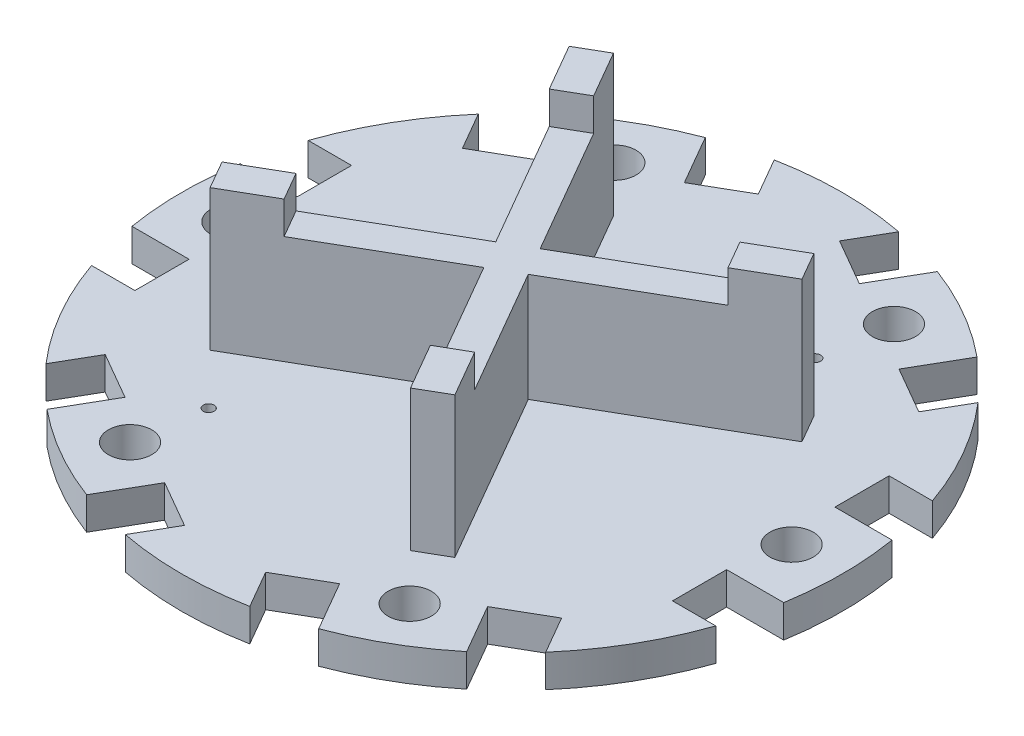
SolidWorks part; units mm, degrees
ref_plane "Alzado" through (0, 0, 0) normal (0, 0, 1) x (1, 0, 0)
ref_plane "Planta" through (0, 0, 0) normal (0, 1, 0) x (1, 0, 0)
ref_plane "Vista lateral" through (0, 0, 0) normal (1, 0, 0) x (0, 0, -1)
sketch "Croquis1" plane through (0, 0, 0) normal (0, 1, 0) x (1, 0, 0)
  circle A0 centre (0, 0) radius 30.5
extrude "Saliente-Extruir1" add sketch "Croquis1" along normal blind 3
sketch "Croquis5" plane through (0, 3, 0) normal (0, 1, 0) x (1, 0, 0)
  line L1 (28.8141, -5) -> (30.0874, -5)
  line L2 (28.8141, 5) -> (30.0874, 5)
  line L3 (-24.8141, 10) -> (-28.8141, 10)
  line L4 (24.8141, -5) -> (24.8141, -10)
  line L5 (-24.8141, -10) -> (-28.8141, -10)
  line L6 (24.8141, -5) -> (28.8141, -5)
  line L7 (24.8141, 5) -> (24.8141, 10)
  line L8 (-24.8141, 5) -> (-28.8141, 5)
  line L9 (-24.8141, 5) -> (-24.8141, 10)
  line L10 (-24.8141, -5) -> (-28.8141, -5)
  line L11 (-24.8141, -5) -> (-24.8141, -10)
  line L12 (24.8141, 5) -> (28.8141, 5)
  line L13 (24.8141, -10) -> (28.8141, -10)
  line L14 (24.8141, 10) -> (28.8141, 10)
  line L15 (-28.8141, 5) -> (-30.0874, 5)
  line L16 (-28.8141, -5) -> (-30.0874, -5)
  line L17 (18.7372, 22.4537) -> (19.3738, 23.5564)
  line L18 (-24.8141, 0) -> (-12.407, -21.4896)
  line L19 (-12.407, -21.4896) -> (12.407, -21.4896)
  line L20 (12.407, -21.4896) -> (24.8141, 0)
  line L21 (24.8141, 0) -> (12.407, 21.4896)
  line L22 (12.407, 21.4896) -> (-12.407, 21.4896)
  line L23 (-12.407, 21.4896) -> (-24.8141, 0)
  line L24 (-21.0673, -16.4896) -> (-23.0673, -19.9537)
  line L25 (-3.7468, -26.4896) -> (-5.7468, -29.9537)
  line L26 (-16.7372, -18.9896) -> (-18.7372, -22.4537)
  line L27 (-16.7372, -18.9896) -> (-21.0673, -16.4896)
  line L28 (-8.0769, -23.9896) -> (-10.0769, -27.4537)
  line L29 (-8.0769, -23.9896) -> (-3.7468, -26.4896)
  line L30 (-18.7372, -22.4537) -> (-19.3738, -23.5564)
  line L31 (-10.0769, -27.4537) -> (-10.7136, -28.5564)
  line L32 (10.0769, 27.4537) -> (10.7136, 28.5564)
  line L33 (16.7372, 18.9896) -> (21.0673, 16.4896)
  line L34 (16.7372, 18.9896) -> (18.7372, 22.4537)
  line L35 (8.0769, 23.9896) -> (3.7468, 26.4896)
  line L36 (8.0769, 23.9896) -> (10.0769, 27.4537)
  line L37 (21.0673, 16.4896) -> (23.0673, 19.9537)
  line L38 (3.7468, 26.4896) -> (5.7468, 29.9537)
  line L39 (-3.7468, 26.4896) -> (-5.7468, 29.9537)
  line L40 (-21.0673, 16.4896) -> (-23.0673, 19.9537)
  line L41 (-8.0769, 23.9896) -> (-10.0769, 27.4537)
  line L42 (-8.0769, 23.9896) -> (-3.7468, 26.4896)
  line L43 (-16.7372, 18.9896) -> (-18.7372, 22.4537)
  line L44 (-16.7372, 18.9896) -> (-21.0673, 16.4896)
  line L45 (-10.0769, 27.4537) -> (-10.7136, 28.5564)
  line L46 (-18.7372, 22.4537) -> (-19.3738, 23.5564)
  line L47 (10.0769, -27.4537) -> (10.7136, -28.5564)
  line L48 (18.7372, -22.4537) -> (19.3738, -23.5564)
  line L49 (8.0769, -23.9896) -> (3.7468, -26.4896)
  line L50 (8.0769, -23.9896) -> (10.0769, -27.4537)
  line L51 (16.7372, -18.9896) -> (21.0673, -16.4896)
  line L52 (16.7372, -18.9896) -> (18.7372, -22.4537)
  line L53 (3.7468, -26.4896) -> (5.7468, -29.9537)
  line L54 (21.0673, -16.4896) -> (23.0673, -19.9537)
  circle A0 centre (0, 0) radius 21.4896 construction
  circle A1 centre (0, 0) radius 30.5 construction
  arc A2 (-28.8141, 10) -> (-30.0874, 5) centre (0, 0) ccw
  arc A3 (-5.7468, 29.9537) -> (-10.7136, 28.5564) centre (0, 0) ccw
  arc A4 (-30.0874, -5) -> (-28.8141, -10) centre (0, 0) ccw
  arc A5 (30.0874, -5) -> (28.8141, -10) centre (0, 0) cw
  arc A6 (28.8141, 10) -> (30.0874, 5) centre (0, 0) cw
  arc A7 (-23.0673, -19.9537) -> (-19.3738, -23.5564) centre (0, 0) ccw
  arc A8 (-10.7136, -28.5564) -> (-5.7468, -29.9537) centre (0, 0) ccw
  arc A9 (-19.3738, 23.5564) -> (-23.0673, 19.9537) centre (0, 0) ccw
  arc A10 (19.3738, 23.5564) -> (23.0673, 19.9537) centre (0, 0) cw
  arc A11 (5.7468, 29.9537) -> (10.7136, 28.5564) centre (0, 0) cw
  arc A12 (10.7136, -28.5564) -> (5.7468, -29.9537) centre (0, 0) cw
  arc A13 (23.0673, -19.9537) -> (19.3738, -23.5564) centre (0, 0) cw
  circle M2 centre (0, 0) radius 30.5
extrude "Cortar-Extruir3" cut sketch "Croquis5" against normal blind 4 contours L15 L8 L9 L3 M2 | L14 L7 L12 L2 M2 | L4 L13 L1 L6 M2 | L54 L51 L52 L48 M2 | L49 L53 L47 L50 M2 | L28 L31 L25 L29 M2 | L30 L26 L27 L24 M2 | L10 L16 L5 L11 M2 | L43 L46 L40 L44 M2 | L45 L41 L42 L39 M2 | L38 L35 L36 L32 M2 | L33 L37 L17 L34 M2 region at (27.1844, 3, 7.3876) region at (19.99, 3, 19.8486) region at (27.1844, 3, -7.3876) region at (7.1944, 3, 27.2362) region at (19.99, 3, -19.8486) region at (-7.1944, 3, 27.2362) region at (7.1944, 3, -27.2362) region at (-19.99, 3, 19.8486) region at (-7.1944, 3, -27.2362) region at (-27.1844, 3, 7.3876) region at (-19.99, 3, -19.8486) region at (-27.1844, 3, -7.3876)
sketch "Croquis7" plane through (0, 3, 0) normal (0, 1, 0) x (1, 0, 0)
  line L2 (25.8141, 0) -> (12.907, 22.3556)
  line L3 (12.907, 22.3556) -> (-12.907, 22.3556)
  line L4 (-12.907, 22.3556) -> (-25.8141, 0)
  line L5 (-25.8141, 0) -> (-12.907, -22.3556)
  line L6 (-12.907, -22.3556) -> (12.907, -22.3556)
  line L7 (12.907, -22.3556) -> (25.8141, 0)
  circle A0 centre (25.8141, 0) radius 2
  circle A4 centre (-25.8141, 0) radius 2
  circle A5 centre (0, 0) radius 22.3556 construction
  circle A6 centre (12.907, 22.3556) radius 2
  circle A7 centre (-12.907, -22.3556) radius 2
  circle A8 centre (-12.907, 22.3556) radius 2
  circle A9 centre (12.907, -22.3556) radius 2
extrude "Cortar-Extruir4" cut sketch "Croquis7" against normal blind 10 contours A8 L4 L3 | A4 L4 L5 | A4 L5 L4 | A8 L3 L4 | L2 A6 L3 | L3 A6 L2 | L7 A0 L2 | L2 A0 L7 | A7 L5 L6 | A7 L6 L5 | L6 A9 L7 | L7 A9 L6 | A4 region at (24.7114, 3, 0) region at (26.3654, 3, 0) region at (12.3557, 3, -21.4007) region at (13.1827, 3, -22.8331) region at (13.1827, 3, 22.8331) region at (12.3557, 3, 21.4007) region at (-12.3557, 3, -21.4007) region at (-13.1827, 3, -22.8331) region at (-13.1827, 3, 22.8331) region at (-12.3557, 3, 21.4007) region at (-24.7114, 3, 0) region at (-26.3654, 3, 0)
sketch "Croquis8" plane through (0, 3, 0) normal (0, 1, 0) x (1, 0, 0)
  line L0 (0, 0) -> (12, 0)
  line L1 (12, 0) -> (12, 16)
  line L2 (0, 0) -> (-12, 0)
  line L3 (-12, 0) -> (-12, -16)
  circle A0 centre (12, 16) radius 0.5
  circle A1 centre (-12, -16) radius 0.5
extrude "Cortar-Extruir5" cut sketch "Croquis8" against normal blind 3 contours A1 | A0 region at (11.6564, 3, -16.3436) region at (-11.6564, 3, 15.6564)
sketch "Croquis9" plane through (0, 3, 0) normal (0, 1, 0) x (1, 0, 0)
  line L0 (16.5705, 11.299) -> (-18.0705, -8.701)
  line L1 (-8.701, 18.0705) -> (11.299, -16.5705)
  line L2 (-10, 17.3205) -> (-8.701, 18.0705)
  line L3 (8.701, -18.0705) -> (-11.299, 16.5705)
  line L4 (-16.5705, -11.299) -> (18.0705, 8.701)
  line L5 (25.6318, 16.5306) -> (27.1318, 13.9325)
  line L6 (-10, 17.3205) -> (-11.299, 16.5705)
  line L7 (17.3205, 10) -> (16.5705, 11.299)
  line L8 (10, -17.3205) -> (8.701, -18.0705)
  line L9 (10, -17.3205) -> (11.299, -16.5705)
  line L11 (-17.3205, -10) -> (-16.5705, -11.299)
  line L12 (-17.3205, -10) -> (-18.0705, -8.701)
  line L14 (17.3205, 10) -> (18.0705, 8.701)
extrude "Saliente-Extruir2" add sketch "Croquis9" along normal blind 10 contours L12 L11 L4 L3 L0 | L3 L4 L1 L0 | L2 L6 L3 L0 L1 | L14 L7 L0 L1 L4 | L8 L9 L1 L4 L3 region at (9.3098, 3, -5.375) region at (0, 3, 0) region at (-5.375, 3, -9.3098) region at (-9.3098, 3, 5.375) region at (5.375, 3, 9.3098)
sketch "Croquis10" plane through (0, 13, 0) normal (0, 1, 0) x (1, 0, 0)
  line L0 (-8.701, 18.0705) -> (-11.299, 16.5705)
  line L1 (-8.701, 18.0705) -> (-6.201, 13.7404)
  line L2 (-11.299, 16.5705) -> (-8.799, 12.2404)
  line L3 (-6.201, 13.7404) -> (-8.799, 12.2404)
  line L6 (-12.2404, -8.799) -> (-13.7404, -6.201)
  line L7 (-18.0705, -8.701) -> (-13.7404, -6.201)
  line L8 (-16.5705, -11.299) -> (-12.2404, -8.799)
  line L9 (-16.5705, -11.299) -> (-18.0705, -8.701)
  line L10 (8.701, -18.0705) -> (11.299, -16.5705)
  line L11 (8.701, -18.0705) -> (6.201, -13.7404)
  line L12 (11.299, -16.5705) -> (8.799, -12.2404)
  line L13 (6.201, -13.7404) -> (8.799, -12.2404)
  line L14 (12.2404, 8.799) -> (13.7404, 6.201)
  line L15 (18.0705, 8.701) -> (13.7404, 6.201)
  line L16 (16.5705, 11.299) -> (12.2404, 8.799)
  line L17 (16.5705, 11.299) -> (18.0705, 8.701)
extrude "Saliente-Extruir3" add sketch "Croquis10" along normal blind 3
